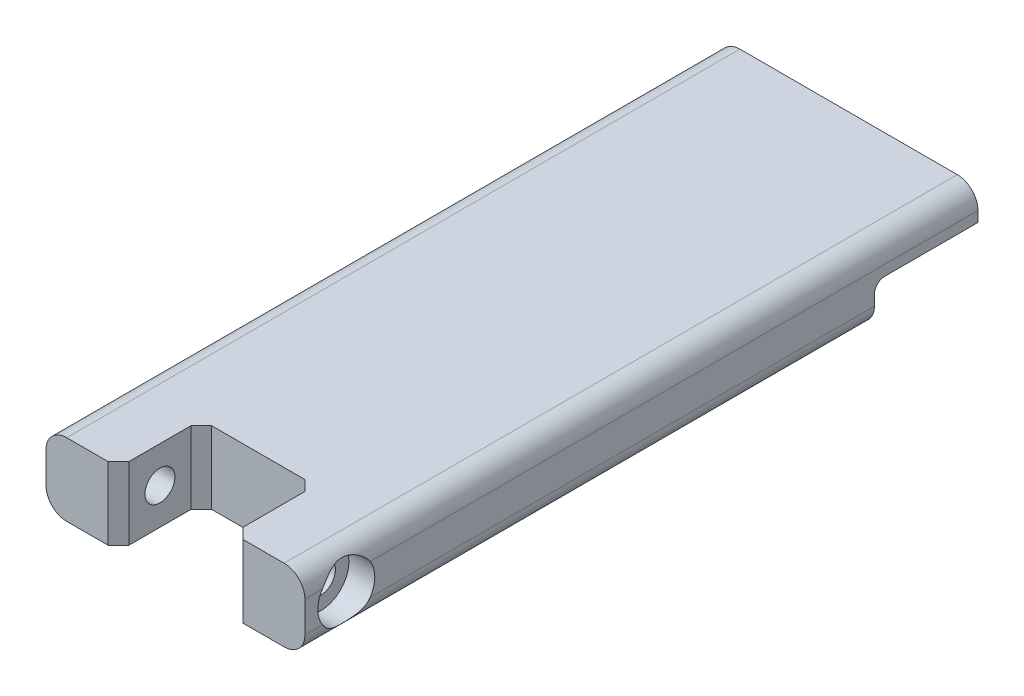
SolidWorks part; units mm, degrees
material "6061-T6 (SS)"
ref_plane "Front Plane" through (0, 0, 0) normal (0, 0, 1) x (1, 0, 0)
ref_plane "Top Plane" through (0, 0, 0) normal (0, 1, 0) x (1, 0, 0)
ref_plane "Right Plane" through (0, 0, 0) normal (1, 0, 0) x (0, 0, -1)
sketch "Sketch1" plane through (0, 0, 0) normal (0, 0, 1) x (1, 0, 0)
  line L1 (-12.5, -3.5) -> (12.5, -3.5)
  line L2 (-12.5, -3.5) -> (-12.5, 3.5)
  line L3 (-12.5, 3.5) -> (12.5, 3.5)
  line L4 (12.5, -3.5) -> (12.5, 3.5)
  line L5 (-12.5, -3.5) -> (12.5, 3.5) construction
  line L6 (-12.5, 3.5) -> (12.5, -3.5) construction
  point P0 (0, 0)
  dimension "D1" = 25
  dimension "D2" = 7
extrude "Boss-Extrude1" add sketch "Sketch1" along normal blind 65
sketch "Sketch2" plane through (0, 3.5, 0) normal (0, 1, 0) x (1, 0, 0)
  line L0 (12.5, -65) -> (-12.5, -65) construction
  line L1 (-5.5, -65) -> (5.5, -65)
  line L2 (-5.5, -65) -> (-5.5, -57)
  line L3 (-5.5, -57) -> (5.5, -57)
  line L4 (5.5, -65) -> (5.5, -57)
  line L5 (12.5, -65) -> (12.5, 0) construction
  line L6 (-12.5, -65) -> (-12.5, 0) construction
  dimension "D1" = 7
  dimension "D2" = 7
  dimension "D3" = 8
extrude "Cut-Extrude1" cut sketch "Sketch2" against normal through all
chamfer "Chamfer1" distance 1 angle 45 2 edges at (5.5, 0, 57) (-5.5, 0, 57)
hole_wizard "CBORE for M2.5 SHCS2" positions "Sketch8" profile "Sketch9" counterbore size "M2.5" standard "ANSI Metric" end condition through all
sketch "Sketch8" plane through (12.5, -6.575, 116.7065) normal (1, 0, 0) x (0, 0, -1)
  point P0 (55.7065, 6.575)
sketch "Sketch9" plane through (12.5, 0, 61) normal (0, 1, 0) x (0, 0, -1)
  line L0 (0, 0) -> (0, 25)
  line L1 (0, 25) -> (1.45, 25)
  line L3 (1.45, 25) -> (1.45, 2.5)
  line L4 (1.45, 2.5) -> (2.75, 2.5)
  line L5 (2.75, 2.5) -> (2.75, 0)
  line L7 (2.75, 0) -> (0, 0)
  line L11 (0, -6.35) -> (0, 107.95) construction
  dimension "Thru Hole Dia." = 2.9
  dimension "Thru Hole Depth" = 25
  dimension "C'Bore Dia." = 5.5
  dimension "C'Bore Depth" = 2.5
fillet "Fillet1" radius 2 4 edges at (-12.5, 3.5, 32.5) (12.5, 3.5, 32.5) (-12.5, -3.5, 32.5) (12.5, -3.5, 32.5)
chamfer "Chamfer2" distance 1 angle 45 2 edges at (5.5, 0, 65) (-5.5, 0, 65)
sketch "Sketch10" plane through (0, 0, 0) normal (0, 0, -1) x (-1, 0, 0)
  line L0 (10.5, -3.5) -> (-10.5, -3.5) construction
  line L1 (-12.5, 0.5) -> (12.5, 0.5)
  line L2 (-12.5, 0.5) -> (-12.5, -3.5)
  line L3 (-12.5, -3.5) -> (12.5, -3.5)
  line L4 (12.5, 0.5) -> (12.5, -3.5)
  line L5 (-12.5, -1.5) -> (-12.5, 1.5) construction
  line L6 (12.5, 1.5) -> (12.5, -1.5) construction
  point P4 (8.659, -1.6119)
  dimension "D1" = 4
extrude "Cut-Extrude2" cut sketch "Sketch10" against normal blind 10
fillet "Fillet2" radius 1 1 edges at (0, 0.5, 10)
